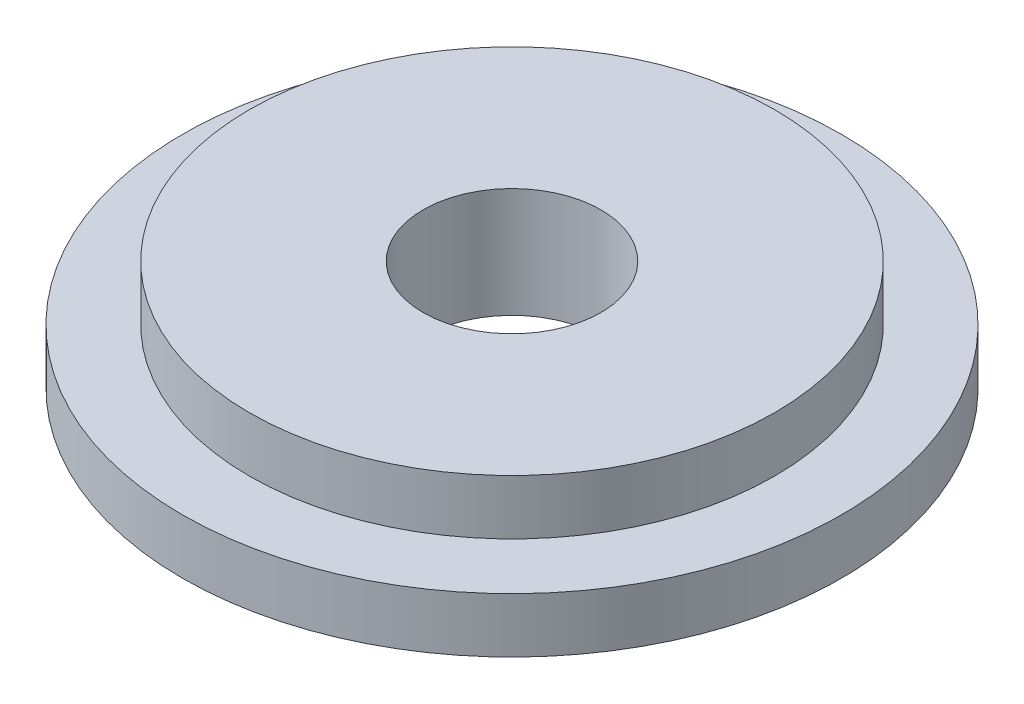
SolidWorks part; units mm, degrees
ref_plane "Front Plane" through (0, 0, 0) normal (0, 0, 1) x (1, 0, 0)
ref_plane "Top Plane" through (0, 0, 0) normal (0, 1, 0) x (1, 0, 0)
ref_plane "Right Plane" through (0, 0, 0) normal (1, 0, 0) x (0, 0, -1)
sketch "Croquis1" plane through (0, 0, 0) normal (0, 1, 0) x (1, 0, 0)
  circle A0 centre (0, 0) radius 23.9
  circle A1 centre (0, 0) radius 30
  circle A2 centre (0, 0) radius 8.1
  dimension "D1" = 47.8
  dimension "D2" = 60
  dimension "D3" = 16.2
extrude "Saliente-Extruir1" add sketch "Croquis1" along normal blind 5 contours A0 A2 region at (-23.224, 0, 0)
extrude "Saliente-Extruir2" add sketch "Croquis1<3>" against normal blind 5 contours A1 A0 | A0 A2 region at (-23.224, 0, 0) region at (-29.1515, 0, 0)
sketch "Croquis1<3>" plane through (0, 0, 0) normal (0, 1, 0) x (1, 0, 0) same geometry as "Croquis1"
equation "\"ID\" = 47.8"
equation "\"D1@Croquis1\"=\"ID\""
equation "\"OD\"= 60"
equation "\"D2@Croquis1\"=\"OD\""
equation "\"Dmandril\"=16.2"
equation "\"D3@Croquis1\"=\"Dmandril\""
